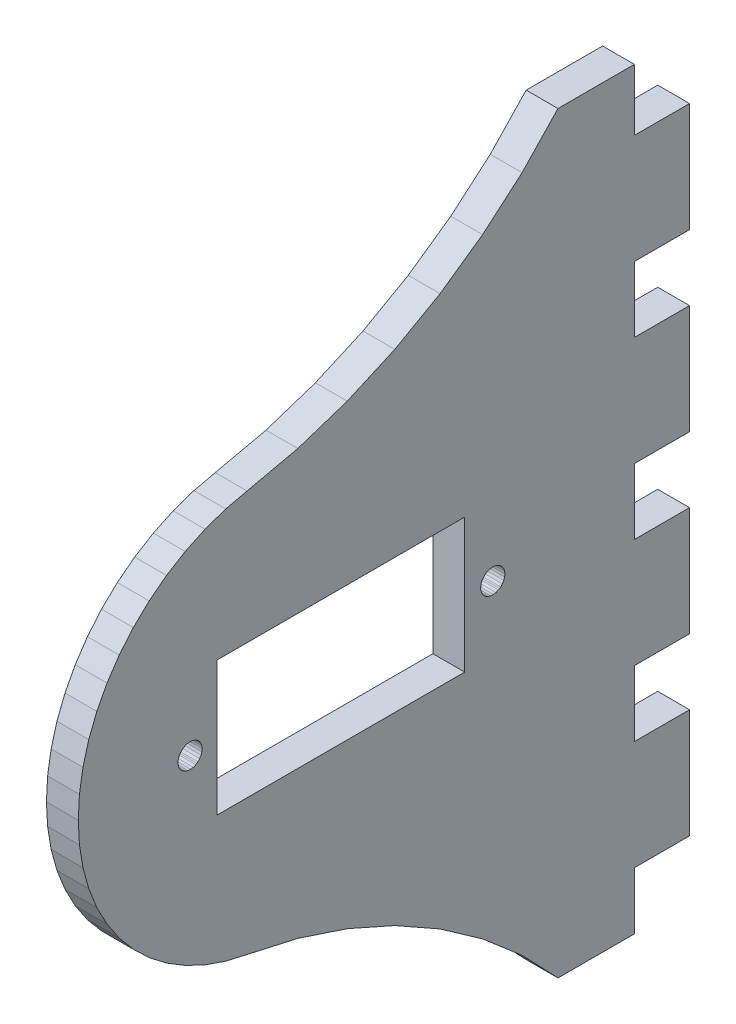
SolidWorks part; units mm, degrees
ref_plane "Front Plane" through (0, 0, 0) normal (0, 0, 1) x (1, 0, 0)
ref_plane "Top Plane" through (0, 0, 0) normal (0, 1, 0) x (1, 0, 0)
ref_plane "Right Plane" through (0, 0, 0) normal (1, 0, 0) x (0, 0, -1)
ref_plane "Plane1" through (3, 0, 0) normal (1, 0, 0) x (0, 0, -1)
sketch "Sketch1" plane through (3, 0, 0) normal (1, 0, 0) x (0, 0, -1)
  line L0 (-22.1268, 14.5669) -> (-23.6186, 13.1379)
  line L1 (-23.6186, 13.1379) -> (-24.9483, 11.5571)
  line L2 (-24.9483, 11.5571) -> (-26.1006, 9.8425)
  line L3 (-26.1006, 9.8425) -> (-27.0621, 8.0142)
  line L4 (-27.0621, 8.0142) -> (-27.8218, 6.0932)
  line L5 (-27.8218, 6.0932) -> (-28.3707, 4.1017)
  line L6 (-28.3707, 4.1017) -> (-28.7026, 2.0628)
  line L7 (-28.7026, 2.0628) -> (-28.8137, 0)
  line L8 (-28.8137, 0) -> (-28.7026, -2.0628)
  line L9 (-28.7026, -2.0628) -> (-28.3707, -4.1017)
  line L10 (-28.3707, -4.1017) -> (-27.8218, -6.0932)
  line L11 (-27.8218, -6.0932) -> (-27.0621, -8.0142)
  line L12 (-27.0621, -8.0142) -> (-26.1006, -9.8425)
  line L13 (-26.1006, -9.8425) -> (-24.9483, -11.5571)
  line L14 (-24.9483, -11.5571) -> (-23.6186, -13.1379)
  line L15 (-23.6186, -13.1379) -> (-22.1268, -14.5669)
  line L16 (-22.1268, -14.5669) -> (-20.4902, -15.8274)
  line L17 (-20.4902, -15.8274) -> (-18.7277, -16.9049)
  line L18 (-18.7277, -16.9049) -> (-16.8597, -17.7869)
  line L19 (-16.8597, -17.7869) -> (-14.9078, -18.4631)
  line L20 (-14.9078, -18.4631) -> (-12.8945, -18.9259)
  line L21 (-12.8945, -18.9259) -> (-8.1098, -20.0013)
  line L22 (-8.1098, -20.0013) -> (-3.453, -21.5389)
  line L23 (-3.453, -21.5389) -> (1.0314, -23.524)
  line L24 (1.0314, -23.524) -> (5.3004, -25.9377)
  line L25 (5.3004, -25.9377) -> (9.3132, -28.7568)
  line L26 (9.3132, -28.7568) -> (13.0314, -31.9544)
  line L27 (13.0314, -31.9544) -> (16.4195, -35.5)
  line L28 (16.4195, -35.5) -> (23.6247, -35.5)
  line L29 (23.6247, -35.5) -> (23.6247, -30.0964)
  line L30 (23.6247, -30.0964) -> (28.8247, -30.0964)
  line L31 (28.8247, -30.0964) -> (28.8247, -19.7964)
  line L32 (28.8247, -19.7964) -> (23.6247, -19.7964)
  line L33 (23.6247, -19.7964) -> (23.6247, -13.5964)
  line L34 (23.6247, -13.5964) -> (28.8247, -13.5964)
  line L35 (28.8247, -13.5964) -> (28.8247, -3.2964)
  line L36 (28.8247, -3.2964) -> (23.6247, -3.2964)
  line L37 (23.6247, -3.2964) -> (23.6247, 2.9036)
  line L38 (23.6247, 2.9036) -> (28.8247, 2.9036)
  line L39 (28.8247, 2.9036) -> (28.8247, 13.2036)
  line L40 (28.8247, 13.2036) -> (23.6247, 13.2036)
  line L41 (23.6247, 13.2036) -> (23.6247, 19.4036)
  line L42 (23.6247, 19.4036) -> (28.8247, 19.4036)
  line L43 (28.8247, 19.4036) -> (28.8247, 29.7036)
  line L44 (28.8247, 29.7036) -> (23.6247, 29.7036)
  line L45 (23.6247, 29.7036) -> (23.6247, 35.5)
  line L46 (23.6247, 35.5) -> (16.4195, 35.5)
  line L47 (16.4195, 35.5) -> (13.0314, 31.9544)
  line L48 (13.0314, 31.9544) -> (9.3132, 28.7568)
  line L49 (9.3132, 28.7568) -> (5.3004, 25.9377)
  line L50 (5.3004, 25.9377) -> (1.0314, 23.524)
  line L51 (1.0314, 23.524) -> (-3.453, 21.5389)
  line L52 (-3.453, 21.5389) -> (-8.1098, 20.0013)
  line L53 (-8.1098, 20.0013) -> (-12.8945, 18.9259)
  line L54 (-12.8945, 18.9259) -> (-14.9078, 18.4631)
  line L55 (-14.9078, 18.4631) -> (-16.8597, 17.7869)
  line L56 (-16.8597, 17.7869) -> (-18.7277, 16.9049)
  line L57 (-18.7277, 16.9049) -> (-20.4902, 15.8274)
  line L58 (-20.4902, 15.8274) -> (-22.1268, 14.5669)
  line L59 (7.6238, -6.1231) -> (-15.7269, -6.1231)
  line L60 (-15.7269, -6.1231) -> (-15.7269, 6.5382)
  line L61 (-15.7269, 6.5382) -> (7.6238, 6.5382)
  line L62 (7.6238, 6.5382) -> (7.6238, -6.1231)
  line L63 (-18.8043, 1.0086) -> (-18.575, 1.1)
  line L64 (-18.575, 1.1) -> (-18.3314, 1.1399)
  line L65 (-18.3314, 1.1399) -> (-18.0849, 1.1266)
  line L66 (-18.0849, 1.1266) -> (-17.847, 1.0605)
  line L67 (-17.847, 1.0605) -> (-17.6289, 0.9449)
  line L68 (-17.6289, 0.9449) -> (-17.5305, 0.8701)
  line L69 (-17.5305, 0.8701) -> (-17.3607, 0.6909)
  line L70 (-17.3607, 0.6909) -> (-17.2335, 0.4793)
  line L71 (-17.2335, 0.4793) -> (-17.1547, 0.2454)
  line L72 (-17.1547, 0.2454) -> (-17.128, 0)
  line L73 (-17.128, 0) -> (-17.1547, -0.2454)
  line L74 (-17.1547, -0.2454) -> (-17.2335, -0.4793)
  line L75 (-17.2335, -0.4793) -> (-17.3607, -0.6909)
  line L76 (-17.3607, -0.6909) -> (-17.5305, -0.8701)
  line L77 (-17.5305, -0.8701) -> (-17.6289, -0.9449)
  line L78 (-17.6289, -0.9449) -> (-17.7348, -1.0086)
  line L79 (-17.7348, -1.0086) -> (-17.9641, -1.1)
  line L80 (-17.9641, -1.1) -> (-18.2077, -1.1399)
  line L81 (-18.2077, -1.1399) -> (-18.4542, -1.1266)
  line L82 (-18.4542, -1.1266) -> (-18.6921, -1.0605)
  line L83 (-18.6921, -1.0605) -> (-18.9102, -0.9449)
  line L84 (-18.9102, -0.9449) -> (-19.0983, -0.7851)
  line L85 (-19.0983, -0.7851) -> (-19.2477, -0.5886)
  line L86 (-19.2477, -0.5886) -> (-19.3514, -0.3645)
  line L87 (-19.3514, -0.3645) -> (-19.4045, -0.1234)
  line L88 (-19.4045, -0.1234) -> (-19.4111, 0)
  line L89 (-19.4111, 0) -> (-19.3845, 0.2454)
  line L90 (-19.3845, 0.2454) -> (-19.3056, 0.4793)
  line L91 (-19.3056, 0.4793) -> (-19.1784, 0.6909)
  line L92 (-19.1784, 0.6909) -> (-19.0086, 0.8701)
  line L93 (-19.0086, 0.8701) -> (-18.8043, 1.0086)
  line L94 (9.7355, 1.0086) -> (9.9648, 1.1)
  line L95 (9.9648, 1.1) -> (10.2084, 1.1399)
  line L96 (10.2084, 1.1399) -> (10.4549, 1.1266)
  line L97 (10.4549, 1.1266) -> (10.6928, 1.0605)
  line L98 (10.6928, 1.0605) -> (10.9109, 0.9449)
  line L99 (10.9109, 0.9449) -> (11.0093, 0.8701)
  line L100 (11.0093, 0.8701) -> (11.1791, 0.6909)
  line L101 (11.1791, 0.6909) -> (11.3063, 0.4793)
  line L102 (11.3063, 0.4793) -> (11.3852, 0.2454)
  line L103 (11.3852, 0.2454) -> (11.4118, 0)
  line L104 (11.4118, 0) -> (11.3852, -0.2454)
  line L105 (11.3852, -0.2454) -> (11.3063, -0.4793)
  line L106 (11.3063, -0.4793) -> (11.1791, -0.6909)
  line L107 (11.1791, -0.6909) -> (11.0093, -0.8701)
  line L108 (11.0093, -0.8701) -> (10.9109, -0.9449)
  line L109 (10.9109, -0.9449) -> (10.805, -1.0086)
  line L110 (10.805, -1.0086) -> (10.5757, -1.1)
  line L111 (10.5757, -1.1) -> (10.3321, -1.1399)
  line L112 (10.3321, -1.1399) -> (10.0856, -1.1266)
  line L113 (10.0856, -1.1266) -> (9.8477, -1.0605)
  line L114 (9.8477, -1.0605) -> (9.6296, -0.9449)
  line L115 (9.6296, -0.9449) -> (9.4415, -0.7851)
  line L116 (9.4415, -0.7851) -> (9.2921, -0.5886)
  line L117 (9.2921, -0.5886) -> (9.1884, -0.3645)
  line L118 (9.1884, -0.3645) -> (9.1353, -0.1234)
  line L119 (9.1353, -0.1234) -> (9.1287, 0)
  line L120 (9.1287, 0) -> (9.1553, 0.2454)
  line L121 (9.1553, 0.2454) -> (9.2342, 0.4793)
  line L122 (9.2342, 0.4793) -> (9.3614, 0.6909)
  line L123 (9.3614, 0.6909) -> (9.5312, 0.8701)
  line L124 (9.5312, 0.8701) -> (9.7355, 1.0086)
  dimension "D1" = 71
  dimension "D2" = 5.2
  dimension "D3" = 10.3
  dimension "D4" = 10.3
  dimension "D5" = 10.3
  dimension "D6" = 10.3
  dimension "D7" = 6.2
  dimension "D8" = 6.2
  dimension "D9" = 6.2
extrude "Boss-Extrude1" add sketch "Sketch1" against normal blind 3
